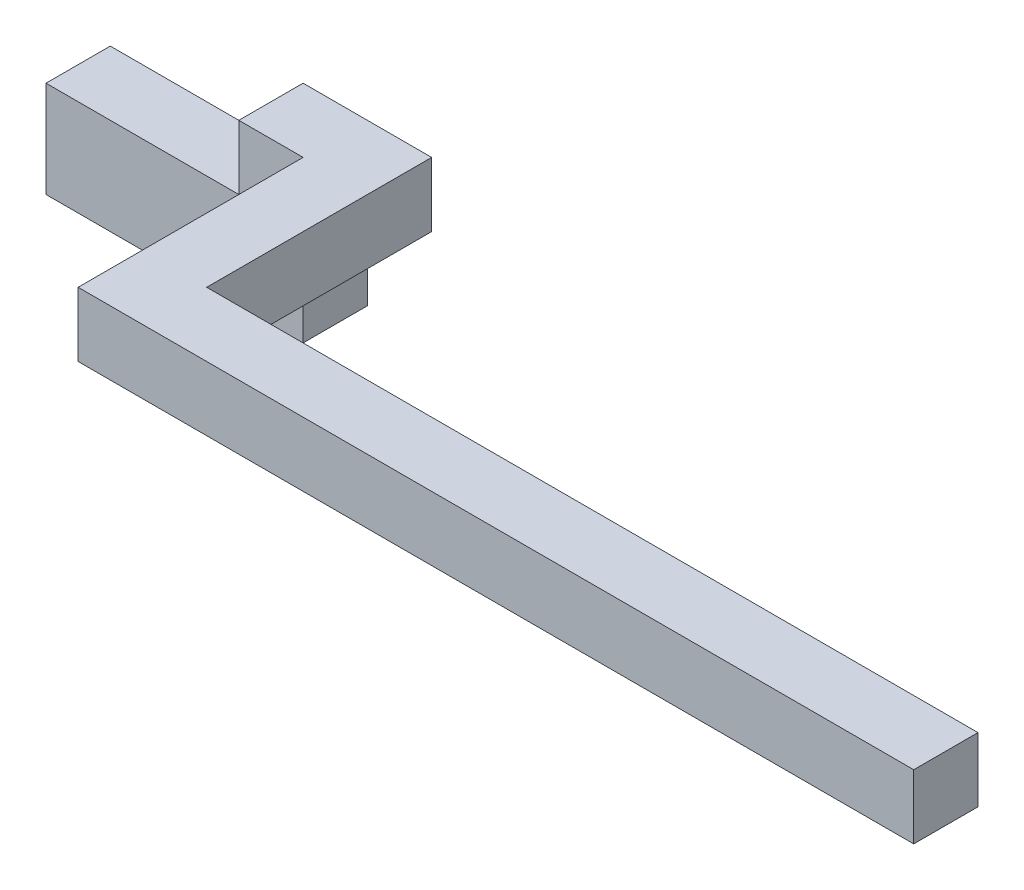
SolidWorks part; units mm, degrees
material "1060 Alloy"
ref_plane "Front Plane" through (0, 0, 0) normal (0, 0, 1) x (1, 0, 0)
ref_plane "Top Plane" through (0, 0, 0) normal (0, 1, 0) x (1, 0, 0)
ref_plane "Right Plane" through (0, 0, 0) normal (1, 0, 0) x (0, 0, -1)
ref_plane "Plane1" through (0, 0, 25.4) normal (0, 0, 1) x (1, 0, 0)
sketch "Sketch1" plane through (0, 0, 25.4) normal (0, 0, 1) x (1, 0, 0)
  line L0 (330.2, 25.4) -> (-101.6, 25.4)
  line L1 (-101.6, 25.4) -> (-101.6, -38.1)
  line L2 (-101.6, -38.1) -> (330.2, -38.1)
  line L3 (330.2, -38.1) -> (330.2, 25.4)
extrude "Boss-Extrude1" add sketch "Sketch1" against normal blind 25.4
sketch "Sketch2" plane through (0, 0, 0) normal (0, 0, -1) x (-1, 0, 0)
  line L0 (0, -38.1) -> (0, 0)
  line L1 (0, 0) -> (-330.2, 0)
  line L2 (-330.2, 0) -> (-330.2, -38.1)
  line L3 (-330.2, -38.1) -> (0, -38.1)
extrude "Cut-Extrude1" cut sketch "Sketch2" against normal through all
sketch "Sketch3" plane through (0, 0, 25.4) normal (0, 0, 1) x (1, 0, 0)
  line L0 (330.2, 0) -> (0, 0)
  line L1 (0, 0) -> (0, 25.4)
  line L2 (0, 25.4) -> (330.2, 25.4)
  line L3 (330.2, 25.4) -> (330.2, 0)
extrude "Boss-Extrude2" add sketch "Sketch3" along normal blind 88.9
sketch "Sketch4" plane through (0, 0, 25.4) normal (0, 0, 1) x (1, 0, 0)
  line L0 (-101.6, 0) -> (-25.4, 0)
  line L1 (-25.4, 0) -> (-25.4, 25.4)
  line L2 (-25.4, 25.4) -> (-101.6, 25.4)
  line L3 (-101.6, 25.4) -> (-101.6, 0)
extrude "Cut-Extrude2" cut sketch "Sketch4" against normal through all
sketch "Sketch5" plane through (0, 25.4, 0) normal (0, 1, 0) x (-1, 0, 0)
  line L0 (-25.4, 0) -> (-25.4, 88.9)
  line L1 (-25.4, 88.9) -> (-330.2, 88.9)
  line L2 (-330.2, 88.9) -> (-330.2, 0)
  line L3 (-330.2, 0) -> (-25.4, 0)
extrude "Cut-Extrude3" cut sketch "Sketch5" against normal through all
hole_wizard "Hole1" positions "Sketch7" profile "Sketch6" legacy
sketch "Sketch7" plane through (0, 0, 0) normal (0, 0, -1) x (-1, 0, 0)
  point P0 (-12.7, 12.7)
sketch "Sketch6" plane through (12.7, 12.7, 0) normal (1, 0, 0) x (0, 1, 0)
  line L0 (0, 0) -> (0, 3.302)
  line L1 (0, 3.302) -> (6.35, 3.302)
  line L2 (6.35, 3.302) -> (6.35, 0)
  line L3 (6.35, 0) -> (0, 0)
  line L4 (0, 110) -> (0, -10) construction
  dimension "Diameter" = 12.7
  dimension "Depth" = 3.302
